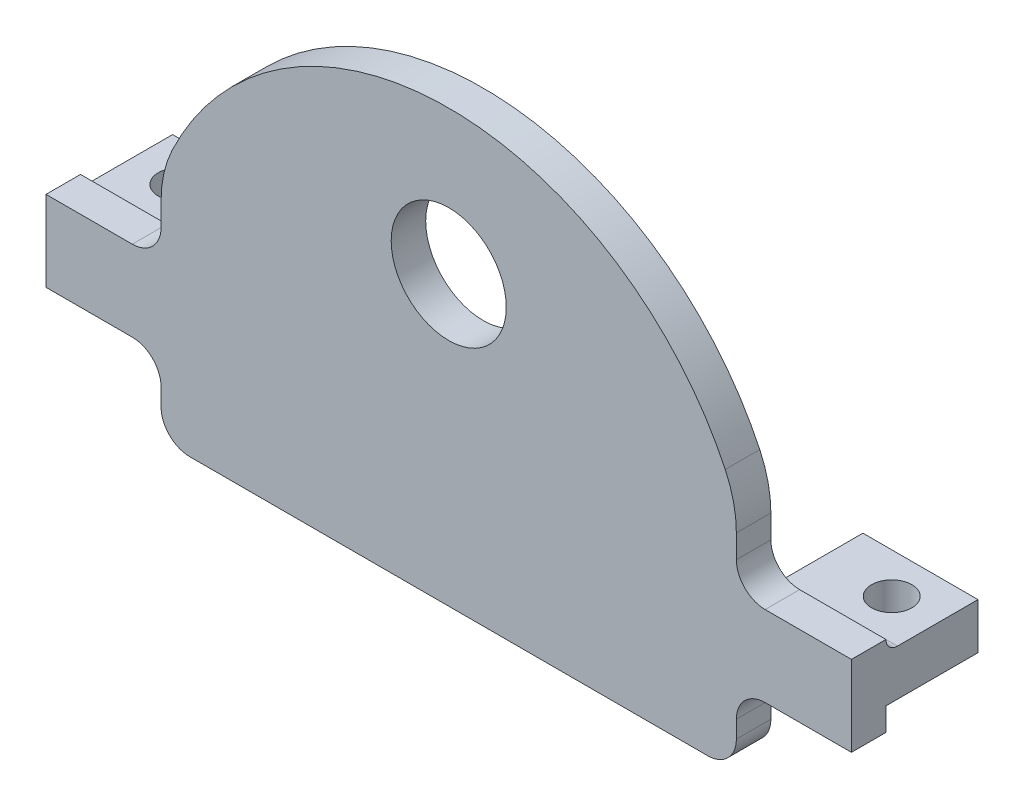
SolidWorks part; units mm, degrees
ref_plane "Front Plane" through (0, 0, 0) normal (0, 0, 1) x (1, 0, 0)
ref_plane "Top Plane" through (0, 0, 0) normal (0, 1, 0) x (1, 0, 0)
ref_plane "Right Plane" through (0, 0, 0) normal (1, 0, 0) x (0, 0, -1)
sketch "Sketch1" plane through (0, 0, 0) normal (0, 0, 1) x (1, 0, 0)
  line L1 (10, 77.5) -> (-10, 77.5)
  line L2 (10, 77.5) -> (10, -77.5)
  line L3 (10, -77.5) -> (-10, -77.5)
  line L4 (-10, 77.5) -> (-10, -77.5)
  line L5 (10, 77.5) -> (-10, -77.5) construction
  line L6 (10, -77.5) -> (-10, 77.5) construction
  point P0 (0, 0)
  dimension "D1" = 20
  dimension "D2" = 155
extrude "Boss-Extrude1" add sketch "Sketch1" along normal blind 4
sketch "Sketch2" plane through (0, 0, 4) normal (0, 0, 1) x (1, 0, 0)
  line L0 (10, -77.5) -> (10, 77.5) construction
  line L1 (-10, -77.5) -> (10, -77.5)
  line L2 (-10, -77.5) -> (-10, -73.5)
  line L3 (-10, -73.5) -> (10, -73.5)
  line L4 (10, -77.5) -> (10, -73.5)
  dimension "D1" = 4
extrude "Boss-Extrude3" add sketch "Sketch2" along normal blind 50 contours L3 L4 L1 L2
sketch "Sketch7" plane through (0, 0, 0) normal (1, 0, 0) x (0, 0, -1)
  line L0 (-29, -73.5) -> (-4, 21.5)
  line L1 (-54, -73.5) -> (-4, -73.5) construction
  line L2 (-4, -73.5) -> (-4, 77.5) construction
  dimension "D1" = 95
  dimension "D2" = 25
rib "Rib2" sketch "Sketch7" sketch "Sketch7" thickness 4 extrusion direction parallel to sketch draft on no parameters "D1"=4
sketch "Sketch8" plane through (0, 0, 4) normal (0, 0, 1) x (1, 0, 0)
  line L0 (-10, 77.5) -> (-10, -73.5) construction
  line L1 (10, 77.5) -> (-10, 77.5)
  line L2 (10, 77.5) -> (10, 74.5)
  line L3 (10, 74.5) -> (-10, 74.5)
  line L4 (-10, 77.5) -> (-10, 74.5)
  dimension "D1" = 3
extrude "Boss-Extrude4" add sketch "Sketch8" along normal blind 3.5
sketch "Sketch9" plane through (0, 0, 7.5) normal (0, 0, 1) x (1, 0, 0)
  line L1 (-35, 79.5) -> (35, 79.5)
  line L2 (-35, 79.5) -> (-35, 74.5)
  line L3 (-35, 74.5) -> (35, 74.5)
  line L4 (35, 79.5) -> (35, 74.5)
  line L5 (10, -73.5) -> (10, 74.5) construction
  line L7 (-10, 74.5) -> (10, 74.5) construction
  dimension "D1" = 70
  dimension "D2" = 25
  dimension "D3" = 5
extrude "Boss-Extrude6" add sketch "Sketch9" along normal blind 3
sketch "Sketch10" plane through (0, 0, 7.5) normal (0, 0, -1) x (-1, 0, 0)
  line L1 (35, 74.5) -> (25, 74.5)
  line L2 (35, 74.5) -> (35, 78.5)
  line L3 (35, 78.5) -> (25, 78.5)
  line L4 (25, 74.5) -> (25, 78.5)
  line L5 (-35, 74.5) -> (-25, 74.5)
  line L6 (-35, 74.5) -> (-35, 78.5)
  line L7 (-35, 78.5) -> (-25, 78.5)
  line L8 (-25, 74.5) -> (-25, 78.5)
  dimension "D1" = 10
  dimension "D2" = 4
extrude "Boss-Extrude7" add sketch "Sketch10" along normal blind 8
sketch "Sketch12" plane through (0, 78.5, 0) normal (0, 1, 0) x (1, 0, 0)
  line L1 (-35, -7.5) -> (-25, -7.5) construction
  line L2 (-35, 0.5) -> (-35, -7.5) construction
  line L3 (35, -7.5) -> (-35, -7.5) construction
  line L4 (35, 0.5) -> (35, -7.5) construction
  circle A0 centre (-31, -3) radius 1.75
  circle A1 centre (31, -3) radius 1.75
  dimension "D1" = 3.5
  dimension "D4" = 3.5
  dimension "D2" = 4.5
  dimension "D3" = 4
  dimension "D5" = 4.5
  dimension "D6" = 4
extrude "Cut-Extrude1" cut sketch "Sketch12" against normal blind 10
sketch "Sketch13" plane through (0, -77.5, 0) normal (0, -1, 0) x (1, 0, 0)
  line L1 (58.3124, -29.3972) -> (-53.0067, -29.3972)
  line L2 (58.3124, -29.3972) -> (58.3124, 70.3466)
  line L3 (58.3124, 70.3466) -> (-53.0067, 70.3466)
  line L4 (-53.0067, -29.3972) -> (-53.0067, 70.3466)
extrude "Cut-Extrude2" cut sketch "Sketch13" against normal up to surface (152 mm away) up to face at (-31, 74.5, 4.75)
sketch "Sketch14" plane through (0, 79.5, 0) normal (0, 1, 0) x (1, 0, 0)
  line L0 (35, -10.5) -> (-35, -10.5) construction
  line L1 (-25, -10.5) -> (25, -10.5)
  line L2 (-25, -10.5) -> (-25, -7.5)
  line L3 (-25, -7.5) -> (25, -7.5)
  line L4 (25, -10.5) -> (25, -7.5)
  line L5 (-25, 0.5) -> (-25, -7.5) construction
  line L6 (25, 0.5) -> (25, -7.5) construction
extrude "Boss-Extrude8" add sketch "Sketch14" along normal blind 6.5
ref_plane "Plane1" through (0, 76, 0) normal (0, -1, 0) x (-1, 0, 0)
mirror "Mirror1" about plane through (0, 76, 0) normal (0, -1, 0) of "Boss-Extrude6", "Boss-Extrude8"
fillet "Fillet1" radius 1 7 edges at (30, 78.5, 7.5) (-30, 78.5, 7.5) (10, 76, 7.5) (-10, 76, 7.5) (0, 77.5, 7.5) (25, 76.5, 7.5) (-25, 76.5, 7.5)
fillet "Fillet2" radius 2.5 6 edges at (-25, 66, 9) (25, 66, 9) (-25, 72.5, 9) (-25, 79.5, 9) (25, 72.5, 9) (25, 79.5, 9)
sketch "Sketch15" plane through (0, 0, 7.5) normal (0, 0, -1) x (-1, 0, 0)
  line L0 (0, 86) -> (0, 91.001) construction
  line L1 (-25, 86) -> (25, 86) construction
  line L2 (0, 78.5) -> (0, 91.001) construction
  line L3 (-11, 78.5) -> (11, 78.5) construction
  line L4 (0, 91.001) -> (0, 103.502) construction
  line L8 (25, 86) -> (-25, 86)
  arc A0 (-25, 86) -> (25, 86) centre (0, 76.8959) cw
  circle A1 centre (0, 91.001) radius 5
  point P12 (0, 91.2153)
  dimension "D1" = 10
  dimension "D2" = 5.001
extrude "Boss-Extrude9" add sketch "Sketch15" against normal up to surface (3 mm away) up to face at (0, 75.1091, 10.5)
fillet "Fillet3" radius 10 2 edges at (25, 86, 9) (-25, 86, 9)
